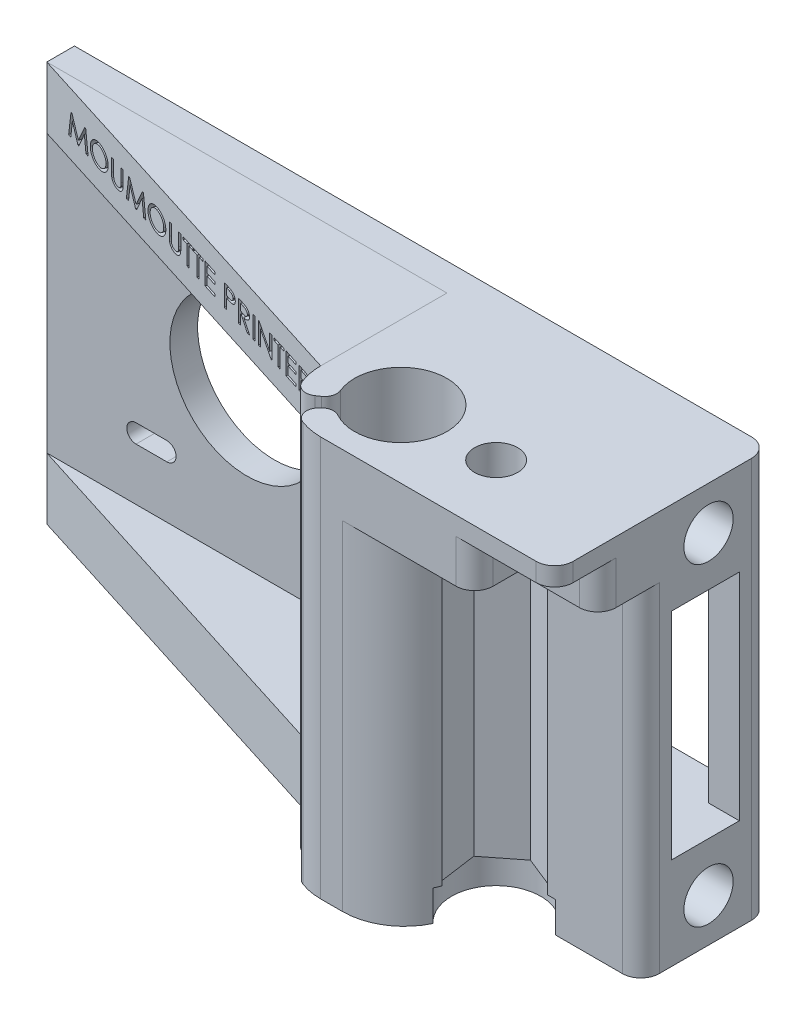
SolidWorks part; units mm, degrees
ref_plane "Front Plane" through (0, 0, 0) normal (0, 0, 1) x (1, 0, 0)
ref_plane "Top Plane" through (0, 0, 0) normal (0, 1, 0) x (1, 0, 0)
ref_plane "Right Plane" through (0, 0, 0) normal (1, 0, 0) x (0, 0, -1)
sketch "Sketch1" plane through (0, 0, 0) normal (0, 1, 0) x (1, 0, 0)
  line L1 (0, 0) -> (48, 0)
  line L2 (0, 0) -> (0, 35)
  line L3 (0, 35) -> (48, 35)
  line L4 (48, 0) -> (48, 35)
  dimension "D1" = 48
  dimension "D2" = 35
extrude "Boss-Extrude1" add sketch "Sketch1" along normal blind 65
sketch "Sketch2" plane through (0, 65, 0) normal (0, 1, 0) x (1, 0, 0)
  line L0 (0, 0) -> (48, 0) construction
  line L1 (0, 35) -> (0, 0) construction
  circle A0 centre (12, 11) radius 7.5
  circle A1 centre (27.5, 11) radius 3.5
  dimension "D1" = 15
  dimension "D5" = 7
  dimension "D6" = 15.5
  dimension "D2" = 11
  dimension "D3" = 12
  dimension "D4" = 11
extrude "Cut-Extrude1" cut sketch "Sketch2" against normal through all
sketch "Sketch3" plane through (48, 0, 0) normal (1, 0, 0) x (0, 0, -1)
  line L0 (0, 65) -> (35, 65) construction
  line L1 (0, 0) -> (14, 0)
  line L2 (0, 0) -> (0, 55)
  line L3 (0, 55) -> (14, 55)
  line L4 (14, 0) -> (14, 55)
  dimension "D1" = 21
  dimension "D2" = 10
extrude "Cut-Extrude2" cut sketch "Sketch3" against normal blind 25
sketch "Sketch4" plane through (48, 0, 0) normal (1, 0, 0) x (0, 0, -1)
  line L0 (14, 0) -> (14, 55) construction
  line L1 (19, 50) -> (30, 50)
  line L2 (19, 50) -> (19, 15)
  line L3 (19, 15) -> (30, 15)
  line L4 (30, 50) -> (30, 15)
  line L5 (35, 65) -> (35, 0) construction
  line L6 (14, 0) -> (35, 0) construction
  line L7 (0, 65) -> (35, 65) construction
  dimension "D1" = 5
  dimension "D2" = 5
  dimension "D3" = 15
  dimension "D4" = 15
extrude "Cut-Extrude3" cut sketch "Sketch4" against normal through all
sketch "Sketch7" plane through (48, 0, 0) normal (1, 0, 0) x (0, 0, -1)
  line L0 (14, 0) -> (35, 0) construction
  line L1 (0, 65) -> (35, 65) construction
  line L2 (35, 65) -> (35, 0) construction
  circle A0 centre (25, 58) radius 4
  circle A1 centre (25, 7) radius 4
  dimension "D1" = 8
  dimension "D2" = 8
  dimension "D3" = 7
  dimension "D4" = 7
  dimension "D5" = 10
  dimension "D6" = 10
extrude "Cut-Extrude4" cut sketch "Sketch7" against normal blind 28.5
sketch "Sketch8" plane through (0, 0, -35) normal (0, 0, -1) x (-1, 0, 0)
  line L0 (-48, 65) -> (0, 65) construction
  line L1 (-5, 15) -> (-43, 15)
  line L2 (-5, 15) -> (-5, 50)
  line L3 (-5, 50) -> (-43, 50)
  line L4 (-43, 15) -> (-43, 50)
  line L5 (-48, 0) -> (0, 0) construction
  line L6 (0, 65) -> (0, 0) construction
  line L7 (-48, 65) -> (-48, 0) construction
  dimension "D1" = 15
  dimension "D2" = 15
  dimension "D3" = 5
  dimension "D4" = 5
extrude "Cut-Extrude5" cut sketch "Sketch8" against normal blind 10
sketch "Sketch9" plane through (48, 0, 0) normal (1, 0, 0) x (0, 0, -1)
  line L1 (0, 55) -> (7, 55)
  line L2 (0, 55) -> (0, 62)
  line L3 (0, 62) -> (7, 62)
  line L4 (7, 55) -> (7, 62)
  dimension "D1" = 7
  dimension "D2" = 7
extrude "Cut-Extrude7" cut sketch "Sketch9" against normal blind 13
fillet "Fillet2" radius 3 5 edges at (48, 63.5, 0) (35, 58.5, 0) (48, 58.5, -7) (48, 27.5, -14) (48, 32.5, -35)
sketch "Sketch10" plane through (0, 0, 0) normal (0, -1, 0) x (1, 0, 0)
  line L1 (26.5765, -17.4934) -> (32.6616, -15.0465)
  line L2 (32.6616, -15.0465) -> (33.5852, -8.5531)
  line L3 (33.5852, -8.5531) -> (28.4235, -4.5066)
  line L4 (28.4235, -4.5066) -> (22.3384, -6.9535)
  line L5 (22.3384, -6.9535) -> (21.4148, -13.4469)
  line L6 (21.4148, -13.4469) -> (26.5765, -17.4934)
  circle A0 centre (27.5, -11) radius 5.68 construction
  dimension "D1" = 11.36
extrude "Cut-Extrude8" cut sketch "Sketch10" against normal blind 60
sketch "Sketch11" plane through (0, 0, 0) normal (0, -1, 0) x (1, 0, 0)
  circle A0 centre (27.5, -11) radius 7.25
  dimension "D1" = 14.5
extrude "Cut-Extrude9" cut sketch "Sketch11" against normal blind 5
fillet "Fillet3" radius 10 2 edges at (23, 27.5, 0) (0, 32.5, 0)
sketch "Sketch12" plane through (0, 65, 0) normal (0, 1, 0) x (1, 0, 0)
  line L0 (1.92, 4.1081) -> (5.8088, 6.7669)
  line L2 (4.0312, 1.9767) -> (7.0354, 5.3784)
  line L3 (7.0354, 5.3784) -> (5.8088, 6.7669)
  line L5 (1.92, 4.1081) -> (1.6822, 3.8703)
  line L6 (1.6822, 3.8703) -> (3.8414, 1.7112)
  line L7 (3.8414, 1.7112) -> (4.0312, 1.9767)
  circle A0 centre (12, 11) radius 7.5 construction
  arc A1 (0, 10) -> (10, 0) centre (10, 10) ccw construction
  dimension "D1" = 3
extrude "Cut-Extrude11" cut sketch "Sketch12" against normal through all
fillet "Fillet4" radius 2 4 edges at (7.0354, 32.5, -5.3784) (5.8088, 32.5, -6.7669) (4.0312, 32.5, -1.9767) (1.92, 32.5, -4.1081)
sketch "Sketch14" plane through (0, 0, -35) normal (0, 0, -1) x (-1, 0, 0)
  line L1 (0, 0) -> (65, 0)
  line L2 (0, 0) -> (0, 65)
  line L3 (0, 65) -> (65, 65)
  line L4 (65, 0) -> (65, 65)
  dimension "D1" = 65
  dimension "D2" = 65
extrude "Boss-Extrude2" add sketch "Sketch14" against normal blind 4.5
sketch "Sketch15" plane through (0, 65, 0) normal (0, 1, 0) x (1, 0, 0)
  line L0 (-65, 30.5) -> (0, 30.5)
  line L1 (0, 30.5) -> (0, 10)
  line L2 (0, 10) -> (-65, 30.5)
extrude "Boss-Extrude3" add sketch "Sketch15" against normal blind 10 separate body
sketch "Sketch16" plane through (0, 0, 0) normal (0, -1, 0) x (1, 0, 0)
  line L0 (-65, -30.5) -> (0, -30.5)
  line L1 (0, -30.5) -> (0, -10)
  line L2 (0, -10) -> (-65, -30.5)
extrude "Boss-Extrude4" add sketch "Sketch16" against normal blind 10
sketch "Sketch17" plane through (0, 0, -30.5) normal (0, 0, 1) x (1, 0, 0)
  line L0 (-19.5, 51) -> (-14.5, 51) construction
  line L1 (-45.5, 20) -> (-50.5, 20) construction
  line L2 (-45.5, 18.5) -> (-50.5, 18.5)
  line L3 (-45.5, 21.5) -> (-50.5, 21.5)
  line L4 (-19.5, 20) -> (-14.5, 20) construction
  line L5 (-19.5, 21.5) -> (-14.5, 21.5)
  line L6 (-19.5, 18.5) -> (-14.5, 18.5)
  line L7 (-65, 10) -> (0, 10) construction
  line L8 (-50.5, 51) -> (-45.5, 51) construction
  line L9 (-50.5, 52.5) -> (-45.5, 52.5)
  line L10 (-50.5, 49.5) -> (-45.5, 49.5)
  line L11 (-19.5, 52.5) -> (-14.5, 52.5)
  line L12 (-19.5, 49.5) -> (-14.5, 49.5)
  line L15 (0, 65) -> (0, 10) construction
  arc A0 (-50.5, 52.5) -> (-50.5, 49.5) centre (-50.5, 51) ccw
  arc A1 (-45.5, 49.5) -> (-45.5, 52.5) centre (-45.5, 51) ccw
  arc A2 (-19.5, 21.5) -> (-19.5, 18.5) centre (-19.5, 20) ccw
  arc A3 (-14.5, 18.5) -> (-14.5, 21.5) centre (-14.5, 20) ccw
  arc A4 (-45.5, 18.5) -> (-45.5, 21.5) centre (-45.5, 20) ccw
  arc A5 (-50.5, 21.5) -> (-50.5, 18.5) centre (-50.5, 20) ccw
  arc A6 (-19.5, 52.5) -> (-19.5, 49.5) centre (-19.5, 51) ccw
  arc A7 (-14.5, 49.5) -> (-14.5, 52.5) centre (-14.5, 51) ccw
  circle A8 centre (-32.5, 35.5) radius 12.5
  point P2 (-48, 51)
  point P7 (-17, 20)
  point P10 (-48, 20)
  point P25 (-17, 51)
  dimension "D2" = 31
  dimension "D3" = 3
  dimension "D4" = 5
  dimension "D16" = 25
  dimension "D5" = 3
  dimension "D6" = 5
  dimension "D7" = 5
  dimension "D8" = 10
  dimension "D9" = 31
  dimension "D10" = 3
  dimension "D11" = 3
  dimension "D12" = 5
  dimension "D13" = 31
  dimension "D14" = 31
  dimension "D15" = 32.5
  dimension "D17" = 15.5
  dimension "D18" = 15.5
extrude "Cut-Extrude12" cut sketch "Sketch17" against normal through all
sketch "Sketch18" plane through (2.8685, 0, -9.0953) normal (-0.3008, 0, 0.9537) x (0.9537, 0, 0.3008)
  text T0 "<b>MOUMOUTTE PRINTER</b>" font "Century Gothic" height 3.5
extrude "Cut-Extrude13" cut sketch "Sketch18" against normal blind 2
